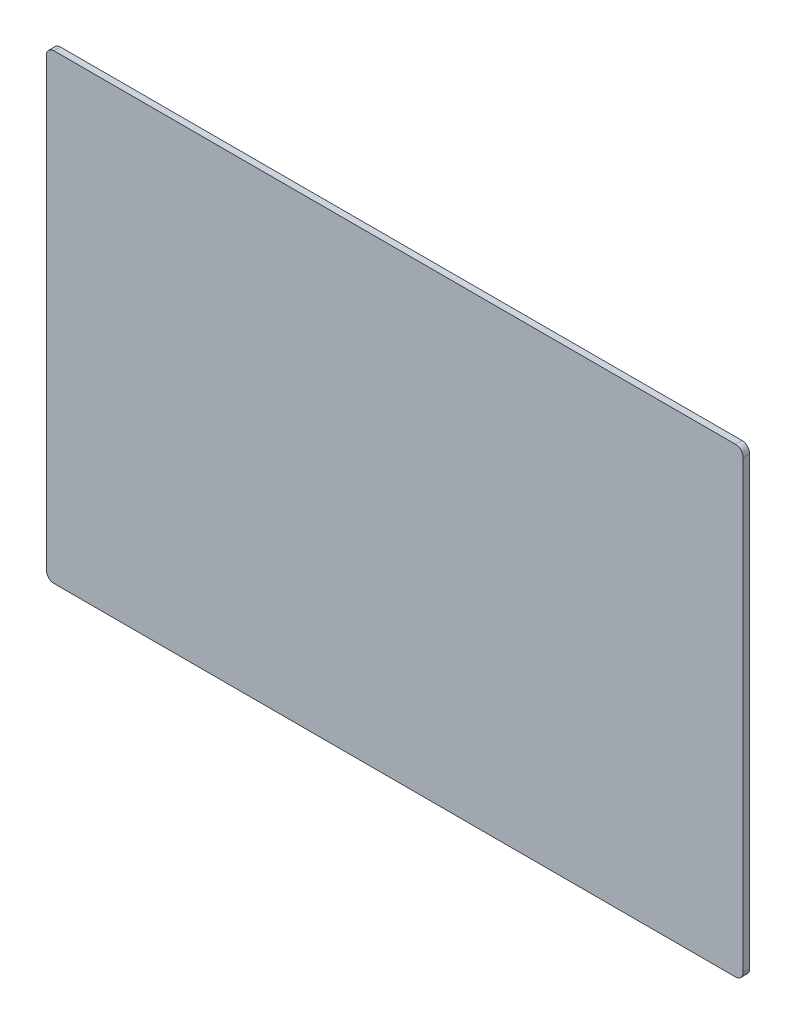
SolidWorks part; units mm, degrees
ref_plane "Front Plane" through (0, 0, 0) normal (0, 0, 1) x (1, 0, 0)
ref_plane "Top Plane" through (0, 0, 0) normal (0, 1, 0) x (1, 0, 0)
ref_plane "Right Plane" through (0, 0, 0) normal (1, 0, 0) x (0, 0, -1)
sketch "Sketch1" plane through (0, 0, 0) normal (0, 0, 1) x (1, 0, 0)
  line L0 (16, 10.2888) -> (-16, 10.2888)
  line L1 (-15.65, -10.9) -> (15.65, -10.9)
  line L2 (-16, -10.55) -> (-16, 10.2888)
  line L4 (16, -10.55) -> (16, 10.2888)
  line L5 (-16, -10.9) -> (16, 10.9) construction
  line L6 (-16, 10.9) -> (16, -10.9) construction
  arc A0 (-16, -10.55) -> (-15.65, -10.9) centre (-15.65, -10.55) ccw
  arc A1 (15.65, -10.9) -> (16, -10.55) centre (15.65, -10.55) ccw
  point P0 (0, 0)
  dimension "D3" = 0.35
  dimension "D1" = 32
  dimension "D2" = 21.8
extrude "Boss-Extrude1" add sketch "Sketch1" along normal blind 0.3
sketch "Sketch2" plane through (0, 0, 0) normal (0, 0, -1) x (-1, 0, 0)
  line L0 (-2.9865, 5.5) -> (-2.9865, 9.5)
  line L1 (-2.8615, 5.625) -> (13.875, 5.625)
  line L2 (-2.8615, 5.625) -> (-2.8615, 9.375)
  line L3 (-2.8615, 9.375) -> (13.875, 9.375)
  line L4 (13.875, 5.625) -> (13.875, 9.375)
  line L5 (-2.9865, 9.5) -> (14, 9.5)
  line L6 (14, 5.5) -> (14, 9.5)
  line L7 (-2.9865, 5.5) -> (14, 5.5)
  line L8 (-2.9865, 1.1) -> (-2.9865, 5.1)
  line L9 (-2.8615, 1.225) -> (13.875, 1.225)
  line L10 (-2.8615, 1.225) -> (-2.8615, 4.975)
  line L11 (-2.8615, 4.975) -> (13.875, 4.975)
  line L12 (13.875, 1.225) -> (13.875, 4.975)
  line L13 (-2.9865, 5.1) -> (14, 5.1)
  line L14 (14, 1.1) -> (14, 5.1)
  line L15 (-2.9865, 1.1) -> (14, 1.1)
  line L16 (-2.9865, -3.3) -> (-2.9865, 0.7)
  line L17 (-2.8615, -3.175) -> (13.875, -3.175)
  line L18 (-2.8615, -3.175) -> (-2.8615, 0.575)
  line L19 (-2.8615, 0.575) -> (13.875, 0.575)
  line L20 (13.875, -3.175) -> (13.875, 0.575)
  line L21 (-2.9865, 0.7) -> (14, 0.7)
  line L22 (14, -3.3) -> (14, 0.7)
  line L23 (-2.9865, -3.3) -> (14, -3.3)
  line L24 (-2.9865, -7.7) -> (-2.9865, -3.7)
  line L25 (-2.8615, -7.575) -> (13.875, -7.575)
  line L26 (-2.8615, -7.575) -> (-2.8615, -3.825)
  line L27 (-2.8615, -3.825) -> (13.875, -3.825)
  line L28 (13.875, -7.575) -> (13.875, -3.825)
  line L29 (-2.9865, -3.7) -> (14, -3.7)
  line L30 (14, -7.7) -> (14, -3.7)
  line L31 (-2.9865, -7.7) -> (14, -7.7)
  line L34 (-13, 1.9) -> (-7.3586, 1.9) construction
  line L35 (-13, 6.9) -> (-7.3586, 6.9) construction
  line L36 (-13, -2.4) -> (-7.3586, -2.4) construction
  line L37 (-13, -6.7) -> (-7.3586, -6.7) construction
  line L38 (-2, 1.9) -> (14, 1.9) construction
  line L39 (0.6336, 7.6649) -> (-0.3645, 7.6649)
  line L40 (-0.3645, 7.6649) -> (-0.3645, 7.9109)
  line L41 (-0.3645, 7.9109) -> (0.6336, 7.9109)
  line L42 (0.6336, 7.9109) -> (0.6336, 7.6649)
  line L43 (-0.4568, 8.8615) -> (-0.6916, 8.744)
  line L44 (-0.5015, 8.484) -> (-0.2667, 8.5987)
  line L45 (0.2337, 7.103) -> (0.8348, 7.103)
  line L46 (0.8348, 7.103) -> (0.8348, 6.8905)
  line L47 (1.0669, 6.7675) -> (1.0669, 7.2986)
  line L48 (0.2337, 7.2735) -> (0.2337, 7.5027)
  line L49 (0.0073, 7.5027) -> (0.0073, 7.2735)
  line L50 (-0.7951, 6.5466) -> (-0.5463, 6.5466)
  line L51 (-0.5463, 6.5466) -> (-0.5463, 7.103)
  line L52 (-0.5463, 7.103) -> (0.0073, 7.103)
  line L53 (0.0073, 7.103) -> (0.0073, 6.8709)
  line L54 (-0.0039, 6.4152) -> (0.2477, 6.4152)
  line L55 (0.2337, 6.8709) -> (0.2337, 7.103)
  line L56 (-1.0299, 8.4813) -> (-1.0299, 7.8997)
  line L57 (-1.0299, 7.8997) -> (-0.8062, 7.8997)
  line L58 (-0.8062, 7.8997) -> (-0.8062, 8.2827)
  line L59 (-0.8062, 8.2827) -> (1.1172, 8.2827)
  line L60 (1.1172, 8.2827) -> (1.1172, 7.9221)
  line L61 (1.1172, 7.9221) -> (1.3465, 7.9221)
  line L62 (1.3465, 7.9221) -> (1.3465, 8.4813)
  line L63 (0.491, 8.4589) -> (0.2533, 8.4589)
  line L64 (0.2533, 8.4589) -> (0.2533, 8.7356)
  line L65 (0.0269, 8.5791) -> (0.0269, 8.4589)
  line L66 (2.7723, 8.2436) -> (2.5737, 8.2017)
  line L67 (2.6995, 7.4328) -> (2.9148, 7.4832)
  line L68 (3.4907, 8.2324) -> (3.2923, 8.1877)
  line L69 (3.4293, 7.4077) -> (3.6613, 7.4608)
  line L70 (2.1656, 8.266) -> (1.9531, 8.2884)
  line L71 (1.7854, 7.3853) -> (2.0454, 7.3406)
  line L72 (3.7731, 8.4952) -> (3.7731, 6.9464)
  line L73 (3.7535, 6.432) -> (4.0135, 6.432)
  line L74 (3.9912, 6.9464) -> (3.9912, 8.635)
  line L75 (2.9931, 8.3555) -> (2.9931, 7.0443)
  line L76 (2.9735, 6.5327) -> (3.2335, 6.5327)
  line L77 (3.214, 7.0443) -> (3.214, 8.4952)
  line L78 (6.6135, 9.0068) -> (6.3927, 8.9034)
  line L79 (6.5381, 8.6406) -> (6.7673, 8.7608)
  line L80 (5.3974, 7.5307) -> (5.6826, 7.5307)
  line L81 (5.3024, 7.2735) -> (5.3974, 7.5307)
  line L82 (6.9267, 8.3331) -> (6.9267, 8.5791)
  line L83 (4.9389, 7.5307) -> (5.2045, 7.5307)
  line L84 (5.4617, 7.7096) -> (5.5484, 7.9445)
  line L85 (5.9063, 7.9277) -> (5.9063, 8.1402)
  line L86 (5.0871, 8.1402) -> (5.0871, 7.9277)
  line L87 (5.2632, 7.7096) -> (4.9501, 7.7096)
  line L88 (4.9557, 8.3526) -> (6.0013, 8.3526)
  line L89 (9.1409, 7.6705) -> (8.9508, 7.5251)
  line L90 (9.5407, 6.7675) -> (9.8091, 6.9604)
  line L91 (8.5034, 7.7096) -> (8.5034, 6.7815)
  line L92 (8.7411, 6.664) -> (8.7411, 7.9585)
  line L93 (8.0114, 8.2716) -> (9.3478, 8.2716)
  line L94 (9.3478, 8.2716) -> (9.1912, 7.9585)
  line L95 (9.1912, 7.9585) -> (9.4596, 7.9277)
  line L96 (9.4596, 7.9277) -> (9.7168, 8.5148)
  line L97 (9.071, 8.498) -> (8.14, 8.498)
  line L98 (11.4361, 8.6015) -> (12.1462, 8.6015)
  line L99 (12.1462, 8.6015) -> (12.1462, 8.2827)
  line L100 (12.1462, 8.2827) -> (11.4361, 8.2827)
  line L101 (11.4361, 8.2827) -> (11.4361, 8.6015)
  line L102 (10.1865, 8.7636) -> (10.1865, 8.5427)
  line L103 (10.4115, 8.5539) -> (10.7666, 8.5539)
  line L104 (10.7666, 8.5539) -> (10.747, 8.1486)
  line L105 (10.747, 8.1486) -> (10.4003, 8.1486)
  line L106 (10.364, 7.4273) -> (10.7092, 7.4273)
  line L107 (10.7624, 7.6034) -> (10.3836, 7.6034)
  line L108 (10.3836, 7.6034) -> (10.4087, 7.9724)
  line L109 (10.4087, 7.9724) -> (10.7582, 7.9724)
  line L110 (11.6514, 7.3686) -> (11.3187, 7.3686)
  line L111 (11.3187, 7.3686) -> (11.3187, 7.6985)
  line L112 (11.3187, 7.6985) -> (11.6514, 7.6985)
  line L113 (11.6514, 7.6985) -> (11.6514, 7.3686)
  line L114 (11.8583, 7.6985) -> (12.205, 7.6985)
  line L115 (12.205, 7.6985) -> (12.205, 7.3686)
  line L116 (12.205, 7.3686) -> (11.8583, 7.3686)
  line L117 (11.8583, 7.3686) -> (11.8583, 7.6985)
  line L118 (11.8583, 7.869) -> (11.8583, 8.1234)
  line L119 (11.6514, 8.1234) -> (11.6514, 7.869)
  line L120 (11.1007, 7.6705) -> (11.1007, 7.2232)
  line L121 (11.095, 7.0135) -> (11.3187, 7.0135)
  line L122 (11.3187, 7.0135) -> (11.3187, 7.198)
  line L123 (11.3187, 7.198) -> (11.6514, 7.198)
  line L124 (11.6514, 7.198) -> (11.6514, 6.7563)
  line L125 (12.3643, 6.4404) -> (12.5852, 6.5382)
  line L126 (12.328, 7.0061) -> (12.149, 6.925)
  line L127 (12.2273, 6.7912) -> (11.8583, 6.7661)
  line L128 (11.8583, 6.7661) -> (11.8583, 7.198)
  line L129 (11.8583, 7.198) -> (12.205, 7.198)
  line L130 (12.205, 7.198) -> (12.205, 7.0699)
  line L131 (12.205, 7.0699) -> (12.4258, 7.0699)
  line L132 (12.4202, 7.2763) -> (12.4202, 7.6705)
  line L133 (-2, -2.4) -> (14, -2.4) construction
  line L134 (-2, -6.7) -> (14, -6.7) construction
  line L135 (-13.6372, -9.9771) -> (14.1623, -9.9771) construction
  spline S0 degree 3 poles (-0.2667, 8.5987) (-0.3422, 8.6797) (-0.4065, 8.7692) (-0.4568, 8.8615) knots 0 0 0 0 0.2 0.2 0.2 0.2
  spline S1 degree 3 poles (-0.6916, 8.744) (-0.5938, 8.6462) (-0.5434, 8.5735) (-0.5015, 8.484) knots 0.4 0.4 0.4 0.4 0.6 0.6 0.6 0.6
  spline S2 degree 3 poles (0.8348, 6.8905) (0.8348, 6.7898) (0.7957, 6.7591) (0.5189, 6.7703) knots 0.068966 0.068966 0.068966 0.068966 0.103448 0.103448 0.103448 0.103448
  spline S3 degree 3 poles (0.5189, 6.7703) (0.5804, 6.6948) (0.614, 6.5997) (0.6112, 6.5187) knots 0.103448 0.103448 0.103448 0.103448 0.137931 0.137931 0.137931 0.137931
  spline S4 degree 3 poles (0.6112, 6.5187) (1.0305, 6.569) (1.0697, 6.6165) (1.0669, 6.7675) knots 0.137931 0.137931 0.137931 0.137931 0.172414 0.172414 0.172414 0.172414
  spline S5 degree 3 poles (1.0669, 7.2986) (0.997, 7.2847) (0.832, 7.2735) (0.2337, 7.2735) knots 0.206897 0.206897 0.206897 0.206897 0.241379 0.241379 0.241379 0.241379
  spline S6 degree 3 poles (0.2337, 7.5027) (0.5525, 7.5027) (0.7454, 7.4999) (0.8656, 7.4999) knots 0.275862 0.275862 0.275862 0.275862 0.310345 0.310345 0.310345 0.310345
  spline S7 degree 3 poles (0.8656, 7.4999) (0.8572, 7.6118) (0.8572, 7.7096) (0.8572, 7.8019) knots 0.310345 0.310345 0.310345 0.310345 0.344828 0.344828 0.344828 0.344828
  spline S8 degree 3 poles (0.8572, 7.8019) (0.8572, 7.9109) (0.86, 8.0116) (0.8656, 8.1038) knots 0.344828 0.344828 0.344828 0.344828 0.37931 0.37931 0.37931 0.37931
  spline S9 degree 3 poles (0.8656, 8.1038) (0.7286, 8.0982) (0.5077, 8.0926) (0.1387, 8.0926) knots 0.37931 0.37931 0.37931 0.37931 0.413793 0.413793 0.413793 0.413793
  spline S10 degree 3 poles (0.1387, 8.0926) (-0.2387, 8.0926) (-0.4568, 8.0955) (-0.591, 8.1038) knots 0.413793 0.413793 0.413793 0.413793 0.448276 0.448276 0.448276 0.448276
  spline S11 degree 3 poles (-0.591, 8.1038) (-0.5854, 8.0199) (-0.5826, 7.9109) (-0.5826, 7.8019) knots 0.448276 0.448276 0.448276 0.448276 0.482759 0.482759 0.482759 0.482759
  spline S12 degree 3 poles (-0.5826, 7.8019) (-0.5826, 7.6901) (-0.5854, 7.581) (-0.5938, 7.4999) knots 0.482759 0.482759 0.482759 0.482759 0.517241 0.517241 0.517241 0.517241
  spline S13 degree 3 poles (-0.5938, 7.4999) (-0.4736, 7.5056) (-0.2863, 7.5056) (0.0073, 7.5027) knots 0.517241 0.517241 0.517241 0.517241 0.551724 0.551724 0.551724 0.551724
  spline S14 degree 3 poles (0.0073, 7.2735) (-0.5686, 7.2735) (-0.7, 7.2819) (-0.7895, 7.2986) knots 0.586207 0.586207 0.586207 0.586207 0.62069 0.62069 0.62069 0.62069
  spline S15 degree 3 poles (-0.7895, 7.2986) (-0.7839, 7.1701) (-0.7811, 7.0387) (-0.7811, 6.9157) knots 0.62069 0.62069 0.62069 0.62069 0.655172 0.655172 0.655172 0.655172
  spline S16 degree 3 poles (-0.7811, 6.9157) (-0.7811, 6.7563) (-0.7839, 6.6612) (-0.7951, 6.5466) knots 0.655172 0.655172 0.655172 0.655172 0.689655 0.689655 0.689655 0.689655
  spline S17 degree 3 poles (0.0073, 6.8709) (0.0073, 6.692) (0.0073, 6.5746) (-0.0039, 6.4152) knots 0.827586 0.827586 0.827586 0.827586 0.862069 0.862069 0.862069 0.862069
  spline S18 degree 3 poles (0.2477, 6.4152) (0.2337, 6.5774) (0.2337, 6.7256) (0.2337, 6.8709) knots 0.896552 0.896552 0.896552 0.896552 0.931034 0.931034 0.931034 0.931034
  spline S19 degree 3 poles (0.0269, 8.4589) (-0.6078, 8.4589) (-0.8733, 8.4645) (-1.0299, 8.4813) knots 0 0 0 0 0.047619 0.047619 0.047619 0.047619
  spline S20 degree 3 poles (1.3465, 8.4813) (1.1116, 8.4673) (0.9103, 8.4617) (0.695, 8.4617) knots 0.380952 0.380952 0.380952 0.380952 0.428571 0.428571 0.428571 0.428571
  spline S21 degree 3 poles (0.695, 8.4617) (0.8432, 8.6574) (0.8852, 8.6909) (0.9271, 8.7133) knots 0.428571 0.428571 0.428571 0.428571 0.47619 0.47619 0.47619 0.47619
  spline S22 degree 3 poles (0.9271, 8.7133) (0.9802, 8.744) (0.9774, 8.7692) (0.9215, 8.786) knots 0.47619 0.47619 0.47619 0.47619 0.52381 0.52381 0.52381 0.52381
  spline S23 degree 3 poles (0.9215, 8.786) (0.8376, 8.8111) (0.7705, 8.8419) (0.7118, 8.8782) knots 0.52381 0.52381 0.52381 0.52381 0.571429 0.571429 0.571429 0.571429
  spline S24 degree 3 poles (0.7118, 8.8782) (0.6699, 8.7636) (0.6084, 8.6518) (0.491, 8.4589) knots 0.571429 0.571429 0.571429 0.571429 0.619048 0.619048 0.619048 0.619048
  spline S25 degree 3 poles (0.2533, 8.7356) (0.2533, 8.786) (0.2701, 8.8698) (0.2897, 8.8894) knots 0.714286 0.714286 0.714286 0.714286 0.761905 0.761905 0.761905 0.761905
  spline S26 degree 3 poles (0.2897, 8.8894) (0.3204, 8.9202) (0.3204, 8.9314) (0.2701, 8.9314) knots 0.761905 0.761905 0.761905 0.761905 0.809524 0.809524 0.809524 0.809524
  spline S27 degree 3 poles (0.2701, 8.9314) (0.1807, 8.9314) (0.0856, 8.9369) (0.0073, 8.9509) knots 0.809524 0.809524 0.809524 0.809524 0.857143 0.857143 0.857143 0.857143
  spline S28 degree 3 poles (0.0073, 8.9509) (0.0185, 8.8838) (0.0269, 8.6993) (0.0269, 8.5791) knots 0.857143 0.857143 0.857143 0.857143 0.904762 0.904762 0.904762 0.904762
  spline S29 degree 3 poles (2.9148, 7.4832) (2.8729, 7.7236) (2.8198, 8.0172) (2.7723, 8.2436) knots 0 0 0 0 0.2 0.2 0.2 0.2
  spline S30 degree 3 poles (2.5737, 8.2017) (2.6353, 7.9724) (2.6772, 7.7208) (2.6995, 7.4328) knots 0.4 0.4 0.4 0.4 0.6 0.6 0.6 0.6
  spline S31 degree 3 poles (3.6613, 7.4608) (3.6165, 7.7208) (3.5578, 7.9808) (3.4907, 8.2324) knots 0 0 0 0 0.2 0.2 0.2 0.2
  spline S32 degree 3 poles (3.2923, 8.1877) (3.3538, 7.964) (3.4041, 7.6928) (3.4293, 7.4077) knots 0.4 0.4 0.4 0.4 0.6 0.6 0.6 0.6
  spline S33 degree 3 poles (1.9531, 8.2884) (1.9447, 7.9473) (1.9, 7.6621) (1.7854, 7.3853) knots 0.2 0.2 0.2 0.2 0.4 0.4 0.4 0.4
  spline S34 degree 3 poles (2.0454, 7.3406) (2.1153, 7.6481) (2.1488, 7.9025) (2.1656, 8.266) knots 0.6 0.6 0.6 0.6 1 1 1 1
  spline S35 degree 3 poles (4.0331, 8.8447) (4.0862, 8.8755) (4.0778, 8.9006) (4.0107, 8.9006) knots 0 0 0 0 0.1 0.1 0.1 0.1
  spline S36 degree 3 poles (4.0107, 8.9006) (3.9101, 8.9006) (3.8486, 8.9062) (3.7424, 8.9285) knots 0.1 0.1 0.1 0.1 0.2 0.2 0.2 0.2
  spline S37 degree 3 poles (3.7424, 8.9285) (3.7591, 8.8643) (3.7731, 8.6909) (3.7731, 8.4952) knots 0.2 0.2 0.2 0.2 0.3 0.3 0.3 0.3
  spline S38 degree 3 poles (3.7731, 6.9464) (3.7731, 6.7954) (3.7675, 6.6193) (3.7535, 6.432) knots 0.4 0.4 0.4 0.4 0.5 0.5 0.5 0.5
  spline S39 degree 3 poles (4.0135, 6.432) (3.9996, 6.6165) (3.9912, 6.7954) (3.9912, 6.9464) knots 0.6 0.6 0.6 0.6 0.7 0.7 0.7 0.7
  spline S40 degree 3 poles (3.9912, 8.635) (3.9912, 8.7692) (3.9996, 8.8251) (4.0331, 8.8447) knots 0.8 0.8 0.8 0.8 1 1 1 1
  spline S41 degree 3 poles (3.2531, 8.7049) (3.3062, 8.7356) (3.2978, 8.7608) (3.2335, 8.7608) knots 0 0 0 0 0.1 0.1 0.1 0.1
  spline S42 degree 3 poles (3.2335, 8.7608) (3.1301, 8.7608) (3.0686, 8.7664) (2.9624, 8.7888) knots 0.1 0.1 0.1 0.1 0.2 0.2 0.2 0.2
  spline S43 degree 3 poles (2.9624, 8.7888) (2.9791, 8.7245) (2.9931, 8.5511) (2.9931, 8.3555) knots 0.2 0.2 0.2 0.2 0.3 0.3 0.3 0.3
  spline S44 degree 3 poles (2.9931, 7.0443) (2.9931, 6.8933) (2.9875, 6.7256) (2.9735, 6.5327) knots 0.4 0.4 0.4 0.4 0.5 0.5 0.5 0.5
  spline S45 degree 3 poles (3.2335, 6.5327) (3.2196, 6.7283) (3.214, 6.8933) (3.214, 7.0443) knots 0.6 0.6 0.6 0.6 0.7 0.7 0.7 0.7
  spline S46 degree 3 poles (3.214, 8.4952) (3.214, 8.6294) (3.2252, 8.6881) (3.2531, 8.7049) knots 0.8 0.8 0.8 0.8 1 1 1 1
  spline S47 degree 3 poles (2.5626, 8.8223) (2.6073, 8.8587) (2.5961, 8.8866) (2.5318, 8.8838) knots 0 0 0 0 0.125 0.125 0.125 0.125
  spline S48 degree 3 poles (2.5318, 8.8838) (2.4647, 8.881) (2.3836, 8.8838) (2.2746, 8.9006) knots 0.125 0.125 0.125 0.125 0.25 0.25 0.25 0.25
  spline S49 degree 3 poles (2.2746, 8.9006) (2.3082, 8.4533) (2.3166, 7.9668) (2.2886, 7.6425) knots 0.25 0.25 0.25 0.25 0.375 0.375 0.375 0.375
  spline S50 degree 3 poles (2.2886, 7.6425) (2.2466, 7.1086) (2.0789, 6.8066) (1.7602, 6.5606) knots 0.375 0.375 0.375 0.375 0.5 0.5 0.5 0.5
  spline S51 degree 3 poles (1.7602, 6.5606) (1.8636, 6.527) (1.9671, 6.4627) (2.023, 6.3985) knots 0.5 0.5 0.5 0.5 0.625 0.625 0.625 0.625
  spline S52 degree 3 poles (2.023, 6.3985) (2.4144, 6.9045) (2.5374, 7.2567) (2.515, 8.5288) knots 0.625 0.625 0.625 0.625 0.75 0.75 0.75 0.75
  spline S53 degree 3 poles (2.515, 8.5288) (2.5123, 8.6993) (2.5318, 8.7972) (2.5626, 8.8223) knots 0.75 0.75 0.75 0.75 1 1 1 1
  spline S54 degree 3 poles (6.7673, 8.7608) (6.7198, 8.8251) (6.6667, 8.909) (6.6135, 9.0068) knots 0 0 0 0 0.2 0.2 0.2 0.2
  spline S55 degree 3 poles (6.3927, 8.9034) (6.4514, 8.8335) (6.5045, 8.7385) (6.5381, 8.6406) knots 0.4 0.4 0.4 0.4 0.6 0.6 0.6 0.6
  spline S56 degree 3 poles (5.6826, 7.5307) (5.6518, 7.3937) (5.6127, 7.2791) (5.5568, 7.184) knots 0.2 0.2 0.2 0.2 0.4 0.4 0.4 0.4
  spline S57 degree 3 poles (5.5568, 7.184) (5.4757, 7.2148) (5.389, 7.2456) (5.3024, 7.2735) knots 0.4 0.4 0.4 0.4 0.6 0.6 0.6 0.6
  spline S58 degree 3 poles (6.0013, 8.3526) (6.0544, 7.746) (6.1355, 7.3098) (6.2166, 7.1057) knots 0 0 0 0 0.020833 0.020833 0.020833 0.020833
  spline S59 degree 3 poles (6.2166, 7.1057) (6.0796, 6.9268) (5.8671, 6.7479) (5.6267, 6.6053) knots 0.020833 0.020833 0.020833 0.020833 0.041667 0.041667 0.041667 0.041667
  spline S60 degree 3 poles (5.6267, 6.6053) (5.7245, 6.5774) (5.8084, 6.5187) (5.8447, 6.4683) knots 0.041667 0.041667 0.041667 0.041667 0.0625 0.0625 0.0625 0.0625
  spline S61 degree 3 poles (5.8447, 6.4683) (6.0404, 6.6305) (6.1886, 6.7675) (6.3088, 6.9128) knots 0.0625 0.0625 0.0625 0.0625 0.083333 0.083333 0.083333 0.083333
  spline S62 degree 3 poles (6.3088, 6.9128) (6.4374, 6.6696) (6.5381, 6.5578) (6.6247, 6.4963) knots 0.083333 0.083333 0.083333 0.083333 0.104167 0.104167 0.104167 0.104167
  spline S63 degree 3 poles (6.6247, 6.4963) (6.7673, 6.3957) (6.8596, 6.4208) (7.005, 6.8625) knots 0.104167 0.104167 0.104167 0.104167 0.125 0.125 0.125 0.125
  spline S64 degree 3 poles (7.005, 6.8625) (6.949, 6.8765) (6.8903, 6.9157) (6.8093, 7.0023) knots 0.125 0.125 0.125 0.125 0.145833 0.145833 0.145833 0.145833
  spline S65 degree 3 poles (6.8093, 7.0023) (6.7589, 6.6221) (6.6639, 6.6389) (6.4458, 7.103) knots 0.145833 0.145833 0.145833 0.145833 0.166667 0.166667 0.166667 0.166667
  spline S66 degree 3 poles (6.4458, 7.103) (6.5604, 7.2875) (6.6387, 7.4944) (6.703, 7.7739) knots 0.166667 0.166667 0.166667 0.166667 0.1875 0.1875 0.1875 0.1875
  spline S67 degree 3 poles (6.703, 7.7739) (6.7422, 7.9445) (6.7785, 8.0199) (6.8009, 8.0284) knots 0.1875 0.1875 0.1875 0.1875 0.208333 0.208333 0.208333 0.208333
  spline S68 degree 3 poles (6.8009, 8.0284) (6.8428, 8.0451) (6.84, 8.0703) (6.8064, 8.0731) knots 0.208333 0.208333 0.208333 0.208333 0.229167 0.229167 0.229167 0.229167
  spline S69 degree 3 poles (6.8064, 8.0731) (6.745, 8.0787) (6.6219, 8.1066) (6.5269, 8.1346) knots 0.229167 0.229167 0.229167 0.229167 0.25 0.25 0.25 0.25
  spline S70 degree 3 poles (6.5269, 8.1346) (6.5017, 7.7404) (6.443, 7.5167) (6.3563, 7.335) knots 0.25 0.25 0.25 0.25 0.270833 0.270833 0.270833 0.270833
  spline S71 degree 3 poles (6.3563, 7.335) (6.2781, 7.5922) (6.2333, 7.978) (6.2193, 8.3526) knots 0.270833 0.270833 0.270833 0.270833 0.291667 0.291667 0.291667 0.291667
  spline S72 degree 3 poles (6.2193, 8.3526) (6.4877, 8.3498) (6.8344, 8.3443) (6.9267, 8.3331) knots 0.291667 0.291667 0.291667 0.291667 0.3125 0.3125 0.3125 0.3125
  spline S73 degree 3 poles (6.9267, 8.5791) (6.8484, 8.5707) (6.6108, 8.5651) (6.2166, 8.5595) knots 0.333333 0.333333 0.333333 0.333333 0.354167 0.354167 0.354167 0.354167
  spline S74 degree 3 poles (6.2166, 8.5595) (6.2166, 8.8279) (6.225, 8.9034) (6.2501, 8.9258) knots 0.354167 0.354167 0.354167 0.354167 0.375 0.375 0.375 0.375
  spline S75 degree 3 poles (6.2501, 8.9258) (6.3004, 8.9733) (6.2948, 8.9873) (6.2333, 8.9789) knots 0.375 0.375 0.375 0.375 0.395833 0.395833 0.395833 0.395833
  spline S76 degree 3 poles (6.2333, 8.9789) (6.1634, 8.9705) (6.0376, 8.9761) (5.9538, 8.9956) knots 0.395833 0.395833 0.395833 0.395833 0.416667 0.416667 0.416667 0.416667
  spline S77 degree 3 poles (5.9538, 8.9956) (5.9593, 8.9062) (5.9677, 8.8) (5.9873, 8.5595) knots 0.416667 0.416667 0.416667 0.416667 0.4375 0.4375 0.4375 0.4375
  spline S78 degree 3 poles (5.9873, 8.5595) (5.3555, 8.5539) (4.8131, 8.5679) (4.6985, 8.5791) knots 0.4375 0.4375 0.4375 0.4375 0.458333 0.458333 0.458333 0.458333
  spline S79 degree 3 poles (4.6985, 8.5791) (4.774, 7.4105) (4.6873, 6.8821) (4.4273, 6.5522) knots 0.458333 0.458333 0.458333 0.458333 0.479167 0.479167 0.479167 0.479167
  spline S80 degree 3 poles (4.4273, 6.5522) (4.5224, 6.5382) (4.5951, 6.5159) (4.6622, 6.4795) knots 0.479167 0.479167 0.479167 0.479167 0.5 0.5 0.5 0.5
  spline S81 degree 3 poles (4.6622, 6.4795) (4.8187, 6.7283) (4.9054, 7.0778) (4.9389, 7.5307) knots 0.5 0.5 0.5 0.5 0.520833 0.520833 0.520833 0.520833
  spline S82 degree 3 poles (5.2045, 7.5307) (5.157, 7.4021) (5.1067, 7.2763) (5.0535, 7.1701) knots 0.541667 0.541667 0.541667 0.541667 0.5625 0.5625 0.5625 0.5625
  spline S83 degree 3 poles (5.0535, 7.1701) (5.2017, 7.1253) (5.3275, 7.0806) (5.4365, 7.0331) knots 0.5625 0.5625 0.5625 0.5625 0.583333 0.583333 0.583333 0.583333
  spline S84 degree 3 poles (5.4365, 7.0331) (5.3052, 6.9101) (5.1151, 6.8318) (4.8327, 6.7675) knots 0.583333 0.583333 0.583333 0.583333 0.604167 0.604167 0.604167 0.604167
  spline S85 degree 3 poles (4.8327, 6.7675) (4.9082, 6.7144) (4.9557, 6.6501) (4.9893, 6.5746) knots 0.604167 0.604167 0.604167 0.604167 0.625 0.625 0.625 0.625
  spline S86 degree 3 poles (4.9893, 6.5746) (5.2772, 6.6752) (5.4757, 6.787) (5.6183, 6.952) knots 0.625 0.625 0.625 0.625 0.645833 0.645833 0.645833 0.645833
  spline S87 degree 3 poles (5.6183, 6.952) (5.7105, 6.9045) (5.7944, 6.8569) (5.8755, 6.801) knots 0.645833 0.645833 0.645833 0.645833 0.666667 0.666667 0.666667 0.666667
  spline S88 degree 3 poles (5.8755, 6.801) (5.9034, 6.8793) (5.937, 6.9436) (5.9845, 7.0135) knots 0.666667 0.666667 0.666667 0.666667 0.6875 0.6875 0.6875 0.6875
  spline S89 degree 3 poles (5.9845, 7.0135) (5.9006, 7.0498) (5.814, 7.0862) (5.7301, 7.1169) knots 0.6875 0.6875 0.6875 0.6875 0.708333 0.708333 0.708333 0.708333
  spline S90 degree 3 poles (5.7301, 7.1169) (5.814, 7.2735) (5.8755, 7.4692) (5.9314, 7.7264) knots 0.708333 0.708333 0.708333 0.708333 0.729167 0.729167 0.729167 0.729167
  spline S91 degree 3 poles (5.9314, 7.7264) (5.8168, 7.7124) (5.6351, 7.7096) (5.4617, 7.7096) knots 0.729167 0.729167 0.729167 0.729167 0.75 0.75 0.75 0.75
  spline S92 degree 3 poles (5.5484, 7.9445) (5.7077, 7.9445) (5.814, 7.9389) (5.9063, 7.9277) knots 0.770833 0.770833 0.770833 0.770833 0.791667 0.791667 0.791667 0.791667
  spline S93 degree 3 poles (5.9063, 8.1402) (5.8056, 8.1262) (5.6854, 8.1234) (5.4953, 8.1234) knots 0.8125 0.8125 0.8125 0.8125 0.833333 0.833333 0.833333 0.833333
  spline S94 degree 3 poles (5.4953, 8.1234) (5.3052, 8.1234) (5.1905, 8.1262) (5.0871, 8.1402) knots 0.833333 0.833333 0.833333 0.833333 0.854167 0.854167 0.854167 0.854167
  spline S95 degree 3 poles (5.0871, 7.9277) (5.1542, 7.9361) (5.2297, 7.9417) (5.3303, 7.9445) knots 0.875 0.875 0.875 0.875 0.895833 0.895833 0.895833 0.895833
  spline S96 degree 3 poles (5.3303, 7.9445) (5.3107, 7.869) (5.2884, 7.7907) (5.2632, 7.7096) knots 0.895833 0.895833 0.895833 0.895833 0.916667 0.916667 0.916667 0.916667
  spline S97 degree 3 poles (4.9501, 7.7096) (4.9613, 7.8997) (4.9641, 8.1234) (4.9557, 8.3526) knots 0.9375 0.9375 0.9375 0.9375 0.958333 0.958333 0.958333 0.958333
  spline S98 degree 3 poles (8.2015, 7.5782) (8.1372, 7.595) (8.0142, 7.6481) (7.9499, 7.6956) knots 0 0 0 0 0.142857 0.142857 0.142857 0.142857
  spline S99 degree 3 poles (7.9499, 7.6956) (7.8772, 7.4496) (7.5864, 7.0554) (7.3544, 6.8569) knots 0.142857 0.142857 0.142857 0.142857 0.285714 0.285714 0.285714 0.285714
  spline S100 degree 3 poles (7.3544, 6.8569) (7.4663, 6.8346) (7.5557, 6.7982) (7.6172, 6.7395) knots 0.285714 0.285714 0.285714 0.285714 0.428571 0.428571 0.428571 0.428571
  spline S101 degree 3 poles (7.6172, 6.7395) (7.7822, 6.9408) (7.9247, 7.1337) (8.0561, 7.349) knots 0.428571 0.428571 0.428571 0.428571 0.571429 0.571429 0.571429 0.571429
  spline S102 degree 3 poles (8.0561, 7.349) (8.1009, 7.4217) (8.168, 7.4972) (8.1931, 7.5056) knots 0.571429 0.571429 0.571429 0.571429 0.714286 0.714286 0.714286 0.714286
  spline S103 degree 3 poles (8.1931, 7.5056) (8.249, 7.5251) (8.2546, 7.5615) (8.2015, 7.5782) knots 0.714286 0.714286 0.714286 0.714286 1 1 1 1
  spline S104 degree 3 poles (9.8091, 6.9604) (9.5882, 7.2064) (9.3645, 7.4496) (9.1409, 7.6705) knots 0 0 0 0 0.2 0.2 0.2 0.2
  spline S105 degree 3 poles (8.9508, 7.5251) (9.1576, 7.3322) (9.3729, 7.0527) (9.5407, 6.7675) knots 0.4 0.4 0.4 0.4 0.6 0.6 0.6 0.6
  spline S106 degree 3 poles (8.7914, 8.0815) (8.8278, 8.1038) (8.8026, 8.129) (8.7523, 8.1234) knots 0 0 0 0 0.1 0.1 0.1 0.1
  spline S107 degree 3 poles (8.7523, 8.1234) (8.6628, 8.115) (8.5482, 8.1206) (8.4727, 8.1402) knots 0.1 0.1 0.1 0.1 0.2 0.2 0.2 0.2
  spline S108 degree 3 poles (8.4727, 8.1402) (8.4895, 8.0507) (8.5034, 7.8969) (8.5034, 7.7096) knots 0.2 0.2 0.2 0.2 0.3 0.3 0.3 0.3
  spline S109 degree 3 poles (8.5034, 6.7815) (8.5034, 6.6752) (8.4531, 6.6501) (8.1512, 6.7088) knots 0.4 0.4 0.4 0.4 0.5 0.5 0.5 0.5
  spline S110 degree 3 poles (8.1512, 6.7088) (8.2295, 6.5857) (8.249, 6.5159) (8.2602, 6.404) knots 0.5 0.5 0.5 0.5 0.6 0.6 0.6 0.6
  spline S111 degree 3 poles (8.2602, 6.404) (8.6908, 6.4544) (8.7411, 6.5019) (8.7411, 6.664) knots 0.6 0.6 0.6 0.6 0.7 0.7 0.7 0.7
  spline S112 degree 3 poles (8.7411, 7.9585) (8.7411, 8.0144) (8.7607, 8.0619) (8.7914, 8.0815) knots 0.8 0.8 0.8 0.8 1 1 1 1
  spline S113 degree 3 poles (8.14, 8.498) (8.263, 8.7217) (8.3273, 8.7888) (8.3916, 8.8111) knots 0 0 0 0 0.076923 0.076923 0.076923 0.076923
  spline S114 degree 3 poles (8.3916, 8.8111) (8.4559, 8.8335) (8.4559, 8.8615) (8.3916, 8.8726) knots 0.076923 0.076923 0.076923 0.076923 0.153846 0.153846 0.153846 0.153846
  spline S115 degree 3 poles (8.3916, 8.8726) (8.3245, 8.8838) (8.1847, 8.9314) (8.0785, 8.9761) knots 0.153846 0.153846 0.153846 0.153846 0.230769 0.230769 0.230769 0.230769
  spline S116 degree 3 poles (8.0785, 8.9761) (7.9499, 8.5819) (7.7151, 8.1821) (7.4299, 7.9109) knots 0.230769 0.230769 0.230769 0.230769 0.307692 0.307692 0.307692 0.307692
  spline S117 degree 3 poles (7.4299, 7.9109) (7.5585, 7.8886) (7.6452, 7.8494) (7.6871, 7.7963) knots 0.307692 0.307692 0.307692 0.307692 0.384615 0.384615 0.384615 0.384615
  spline S118 degree 3 poles (7.6871, 7.7963) (7.8157, 7.9696) (7.9163, 8.1122) (8.0114, 8.2716) knots 0.384615 0.384615 0.384615 0.384615 0.461538 0.461538 0.461538 0.461538
  spline S119 degree 3 poles (9.7168, 8.5148) (9.605, 8.5036) (9.4176, 8.498) (9.071, 8.498) knots 0.769231 0.769231 0.769231 0.769231 0.846154 0.846154 0.846154 0.846154
  spline S120 degree 3 poles (11.0084, 8.7636) (10.9082, 8.7496) (10.713, 8.744) (10.5611, 8.744) knots 0 0 0 0 0.04 0.04 0.04 0.04
  spline S121 degree 3 poles (10.5611, 8.744) (10.4344, 8.744) (10.2978, 8.7496) (10.1865, 8.7636) knots 0.04 0.04 0.04 0.04 0.08 0.08 0.08 0.08
  spline S122 degree 3 poles (10.1865, 8.5427) (10.2671, 8.5539) (10.3225, 8.5539) (10.4115, 8.5539) knots 0.12 0.12 0.12 0.12 0.16 0.16 0.16 0.16
  spline S123 degree 3 poles (10.4003, 8.1486) (10.3281, 8.1486) (10.2727, 8.1514) (10.2116, 8.1626) knots 0.28 0.28 0.28 0.28 0.32 0.32 0.32 0.32
  spline S124 degree 3 poles (10.2116, 8.1626) (10.2144, 8.101) (10.2088, 7.9696) (10.2004, 7.8131) knots 0.32 0.32 0.32 0.32 0.36 0.36 0.36 0.36
  spline S125 degree 3 poles (10.2004, 7.8131) (10.1921, 7.6565) (10.1809, 7.5503) (10.1669, 7.4161) knots 0.36 0.36 0.36 0.36 0.4 0.4 0.4 0.4
  spline S126 degree 3 poles (10.1669, 7.4161) (10.2256, 7.4245) (10.2894, 7.4273) (10.364, 7.4273) knots 0.4 0.4 0.4 0.4 0.44 0.44 0.44 0.44
  spline S127 degree 3 poles (10.7092, 7.4273) (10.6841, 6.9212) (10.6729, 6.843) (10.6333, 6.7731) knots 0.48 0.48 0.48 0.48 0.52 0.52 0.52 0.52
  spline S128 degree 3 poles (10.6333, 6.7731) (10.5997, 6.7199) (10.4199, 6.6808) (10.2088, 6.7283) knots 0.52 0.52 0.52 0.52 0.56 0.56 0.56 0.56
  spline S129 degree 3 poles (10.2088, 6.7283) (10.2922, 6.6053) (10.3197, 6.5075) (10.3253, 6.4516) knots 0.56 0.56 0.56 0.56 0.6 0.6 0.6 0.6
  spline S130 degree 3 poles (10.3253, 6.4516) (10.8099, 6.4907) (10.8798, 6.5774) (10.9021, 6.9911) knots 0.6 0.6 0.6 0.6 0.64 0.64 0.64 0.64
  spline S131 degree 3 poles (10.9021, 6.9911) (10.9217, 7.3015) (10.9385, 7.5307) (10.9525, 7.6118) knots 0.64 0.64 0.64 0.64 0.68 0.68 0.68 0.68
  spline S132 degree 3 poles (10.9525, 7.6118) (10.9133, 7.6062) (10.8379, 7.6034) (10.7624, 7.6034) knots 0.68 0.68 0.68 0.68 0.72 0.72 0.72 0.72
  spline S133 degree 3 poles (10.7582, 7.9724) (10.836, 7.9724) (10.9026, 7.9696) (10.9525, 7.9612) knots 0.84 0.84 0.84 0.84 0.88 0.88 0.88 0.88
  spline S134 degree 3 poles (10.9525, 7.9612) (10.9553, 8.0926) (10.9609, 8.2017) (10.9721, 8.3918) knots 0.88 0.88 0.88 0.88 0.92 0.92 0.92 0.92
  spline S135 degree 3 poles (10.9721, 8.3918) (10.9832, 8.5819) (10.9916, 8.6574) (11.0084, 8.7636) knots 0.92 0.92 0.92 0.92 1 1 1 1
  spline S136 degree 3 poles (11.8583, 8.1234) (12.1966, 8.1234) (12.2888, 8.1234) (12.3727, 8.1178) knots 0.027778 0.027778 0.027778 0.027778 0.055556 0.055556 0.055556 0.055556
  spline S137 degree 3 poles (12.3727, 8.1178) (12.3699, 8.1989) (12.3671, 8.3247) (12.3671, 8.4617) knots 0.055556 0.055556 0.055556 0.055556 0.083333 0.083333 0.083333 0.083333
  spline S138 degree 3 poles (12.3671, 8.4617) (12.3671, 8.5987) (12.3699, 8.7133) (12.3727, 8.7944) knots 0.083333 0.083333 0.083333 0.083333 0.111111 0.111111 0.111111 0.111111
  spline S139 degree 3 poles (12.3727, 8.7944) (12.2804, 8.786) (12.191, 8.7832) (11.7968, 8.7832) knots 0.111111 0.111111 0.111111 0.111111 0.138889 0.138889 0.138889 0.138889
  spline S140 degree 3 poles (11.7968, 8.7832) (11.4054, 8.7832) (11.3159, 8.786) (11.2237, 8.7944) knots 0.138889 0.138889 0.138889 0.138889 0.166667 0.166667 0.166667 0.166667
  spline S141 degree 3 poles (11.2237, 8.7944) (11.2265, 8.7133) (11.2292, 8.5987) (11.2292, 8.4617) knots 0.166667 0.166667 0.166667 0.166667 0.194444 0.194444 0.194444 0.194444
  spline S142 degree 3 poles (11.2292, 8.4617) (11.2292, 8.3247) (11.2265, 8.1989) (11.2237, 8.1178) knots 0.194444 0.194444 0.194444 0.194444 0.222222 0.222222 0.222222 0.222222
  spline S143 degree 3 poles (11.2237, 8.1178) (11.302, 8.1234) (11.383, 8.1234) (11.6514, 8.1234) knots 0.222222 0.222222 0.222222 0.222222 0.25 0.25 0.25 0.25
  spline S144 degree 3 poles (11.6514, 7.869) (11.3858, 7.869) (11.1873, 7.8718) (11.095, 7.8802) knots 0.277778 0.277778 0.277778 0.277778 0.305556 0.305556 0.305556 0.305556
  spline S145 degree 3 poles (11.095, 7.8802) (11.1007, 7.8186) (11.1007, 7.7683) (11.1007, 7.6705) knots 0.305556 0.305556 0.305556 0.305556 0.333333 0.333333 0.333333 0.333333
  spline S146 degree 3 poles (11.1007, 7.2232) (11.1007, 7.1617) (11.1007, 7.1114) (11.095, 7.0135) knots 0.361111 0.361111 0.361111 0.361111 0.388889 0.388889 0.388889 0.388889
  spline S147 degree 3 poles (11.6514, 6.7563) (11.3998, 6.7479) (11.1454, 6.7507) (10.9692, 6.7619) knots 0.5 0.5 0.5 0.5 0.527778 0.527778 0.527778 0.527778
  spline S148 degree 3 poles (10.9692, 6.7619) (10.9888, 6.6836) (11.0028, 6.6053) (11.0084, 6.5159) knots 0.527778 0.527778 0.527778 0.527778 0.555556 0.555556 0.555556 0.555556
  spline S149 degree 3 poles (11.0084, 6.5159) (11.2963, 6.5522) (11.5452, 6.5718) (12.3, 6.6249) knots 0.555556 0.555556 0.555556 0.555556 0.583333 0.583333 0.583333 0.583333
  spline S150 degree 3 poles (12.3, 6.6249) (12.3252, 6.5606) (12.3475, 6.4963) (12.3643, 6.4404) knots 0.583333 0.583333 0.583333 0.583333 0.611111 0.611111 0.611111 0.611111
  spline S151 degree 3 poles (12.5852, 6.5382) (12.5041, 6.6701) (12.3867, 6.8858) (12.328, 7.0061) knots 0.638889 0.638889 0.638889 0.638889 0.666667 0.666667 0.666667 0.666667
  spline S152 degree 3 poles (12.149, 6.925) (12.1742, 6.8886) (12.2022, 6.8416) (12.2273, 6.7912) knots 0.694444 0.694444 0.694444 0.694444 0.722222 0.722222 0.722222 0.722222
  spline S153 degree 3 poles (12.4258, 7.0699) (12.4202, 7.1482) (12.4202, 7.2204) (12.4202, 7.2763) knots 0.861111 0.861111 0.861111 0.861111 0.888889 0.888889 0.888889 0.888889
  spline S154 degree 3 poles (12.4202, 7.6705) (12.4202, 7.7711) (12.4202, 7.8298) (12.423, 7.8802) knots 0.916667 0.916667 0.916667 0.916667 0.944444 0.944444 0.944444 0.944444
  spline S155 degree 3 poles (12.423, 7.8802) (12.3503, 7.8746) (12.1211, 7.869) (11.8583, 7.869) knots 0.944444 0.944444 0.944444 0.944444 1 1 1 1
  text T0 "SIZE" font "Arial Narrow" height 1.8
  text T2 "MODEL" font "Arial Narrow" height 1.8
  text T3 "RATIO" font "Arial Narrow" height 1.8
  text T4 "DATE" font "Arial Narrow" height 1.8
  text T5 "   RV    30" font "Arial Narrow" height 1.8
  text T6 "1 :15-90" font "Arial Narrow" height 1.8
  text T7 "2023 / 2" font "Arial Narrow" height 1.8
  text T8 "www.cawe || done. com" font "Arial Narrow" height 1.6
  dimension "D1" = 0.125
  dimension "D2" = 4
fillet "Fillet1" radius 0.35 2 edges at (-16, 10.2888, 0.15) (16, 10.2888, 0.15)
extrude "Cut-Extrude2" cut sketch "Sketch2" against normal blind 0.1
